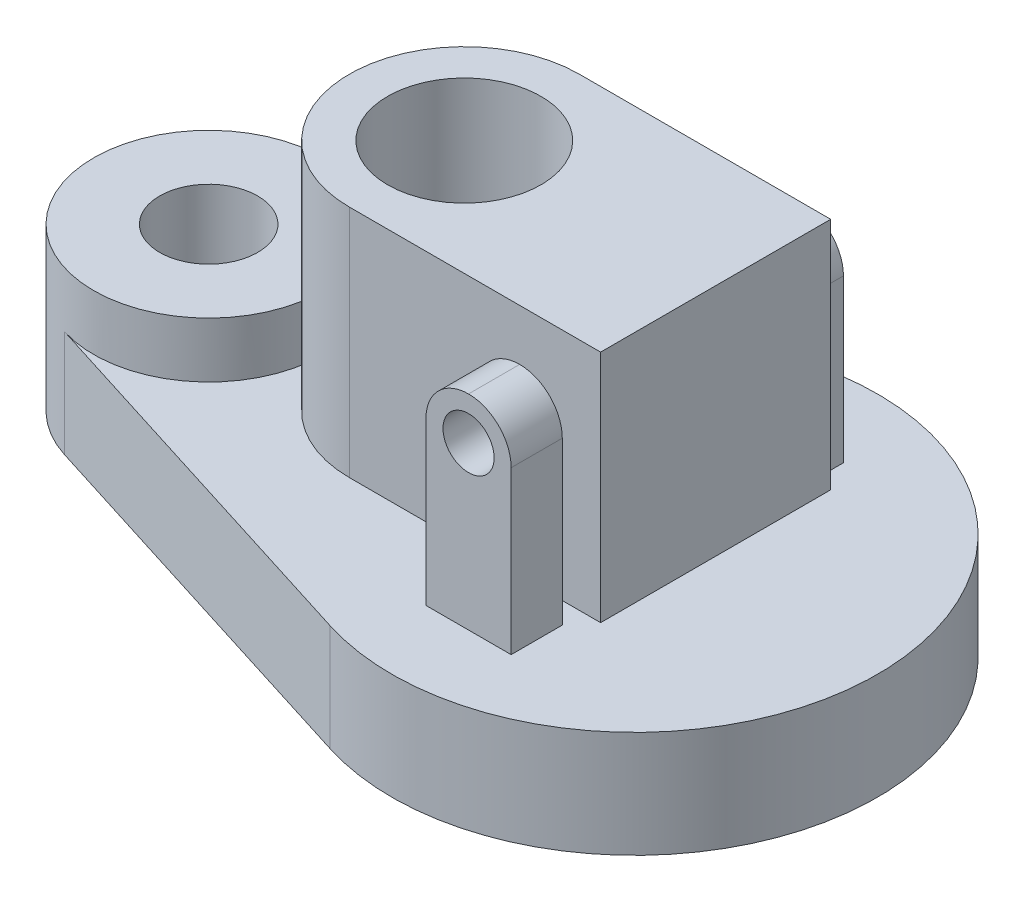
SolidWorks part; units mm, degrees
ref_plane "Front Plane" through (0, 0, 0) normal (0, 0, 1) x (1, 0, 0)
ref_plane "Top Plane" through (0, 0, 0) normal (0, 1, 0) x (1, 0, 0)
ref_plane "Right Plane" through (0, 0, 0) normal (1, 0, 0) x (0, 0, -1)
sketch "Sketch1" plane through (0, 0, 0) normal (0, 1, 0) x (1, 0, 0)
  line L0 (0, 0) -> (-100, 0) construction
  line L1 (-108.1, -25.7564) -> (-17.1, -54.3745)
  line L2 (-108.1, 25.7564) -> (-17.1, 54.3745)
  arc A1 (-108.1, 25.7564) -> (-108.1, -25.7564) centre (-100, 0) ccw
  arc A2 (-17.1, -54.3745) -> (-17.1, 54.3745) centre (0, 0) ccw
  dimension "D1" = 100
  dimension "D2" = 54
  dimension "D3" = 57
extrude "base" add sketch "Sketch1" along normal blind 25
sketch "Sketch2" plane through (0, 25, 0) normal (0, 1, 0) x (1, 0, 0)
  line L0 (0, 0) -> (-100, 0) construction
  circle A0 centre (-100, 0) radius 11.5
  circle A1 centre (-100, 0) radius 27
  dimension "D1" = 23
  dimension "D3" = 54
  dimension "D2" = 100
extrude "front thru border" add sketch "Sketch2" along normal blind 13
sketch "Sketch4" plane through (0, 25, 0) normal (0, 1, 0) x (1, 0, 0)
  line L0 (-100, 0) -> (0, 0) construction
  circle A0 centre (-100, 0) radius 11.5
  circle A1 centre (-100, 0) radius 11.5 construction
  dimension "D1" = 23
extrude "front thru hole" cut sketch "Sketch4" against normal through all
sketch "Sketch5" plane through (0, 25, 0) normal (0, 1, 0) x (1, 0, 0)
  line L0 (0, 27) -> (0, -27) construction
  line L1 (0, -27) -> (-40, -27)
  line L3 (0, 27) -> (-40, 27)
  line L4 (0, 27) -> (19, 27)
  line L6 (0, -27) -> (19, -27)
  line L7 (19, 27) -> (19, -27)
  arc A0 (-40, 27) -> (-40, -27) centre (-40, 0) ccw
  point P4 (0, 0)
  dimension "D4" = 27
  dimension "D1" = 54
  dimension "D2" = 40
  dimension "D3" = 40
  dimension "D5" = 19
extrude "top feature" add sketch "Sketch5" along normal blind 60
sketch "Sketch6" plane through (0, 85, 0) normal (0, 1, 0) x (1, 0, 0)
  line L0 (-40, 27) -> (-40, -27) construction
  circle A0 centre (-40, 0) radius 18
  dimension "D1" = 36
extrude "top feature hole" cut sketch "Sketch6" against normal blind 60
sketch "Sketch7" plane through (0, 0, 27) normal (0, 0, 1) x (1, 0, 0)
  line L1 (19, 25) -> (-71, 25)
  line L2 (19, 25) -> (19, 30)
  line L3 (19, 30) -> (-71, 30)
  line L4 (-71, 25) -> (-71, 30)
  dimension "D1" = 5
  dimension "D2" = 90
extrude "top feature gap" cut sketch "Sketch7" against normal through all
sketch "Sketch8" plane through (0, 25, 0) normal (0, 1, 0) x (1, 0, 0)
  line L0 (0, 0) -> (105.5112, 0) construction
  line L1 (-10, -27) -> (10, -27)
  line L2 (-10, -27) -> (-10, -39)
  line L3 (-10, -39) -> (10, -39)
  line L4 (10, -27) -> (10, -39)
  line L5 (-40, -27) -> (19, -27) construction
  line L6 (-10, 39) -> (10, 39)
  line L7 (10, 27) -> (10, 39)
  line L8 (-10, 27) -> (10, 27)
  line L9 (-10, 27) -> (-10, 39)
  line L10 (19, 27) -> (-40, 27) construction
  point P5 (0, -27)
  dimension "D1" = 12
  dimension "D2" = 20
extrude "top feature arm" add sketch "Sketch8" along normal blind 48
fillet "Fillet2" radius 10 4 edges at (10, 73, -33) (-10, 73, -33) (10, 73, 33) (-10, 73, 33)
sketch "Sketch10" plane through (0, 0, 39) normal (0, 0, 1) x (1, 0, 0)
  line L0 (0, 25) -> (0, 63) construction
  line L1 (-10, 25) -> (10, 25) construction
  circle A0 centre (0, 63) radius 6
  dimension "D1" = 38
  dimension "D2" = 12
extrude "top feature arm hole" cut sketch "Sketch10" against normal through all
